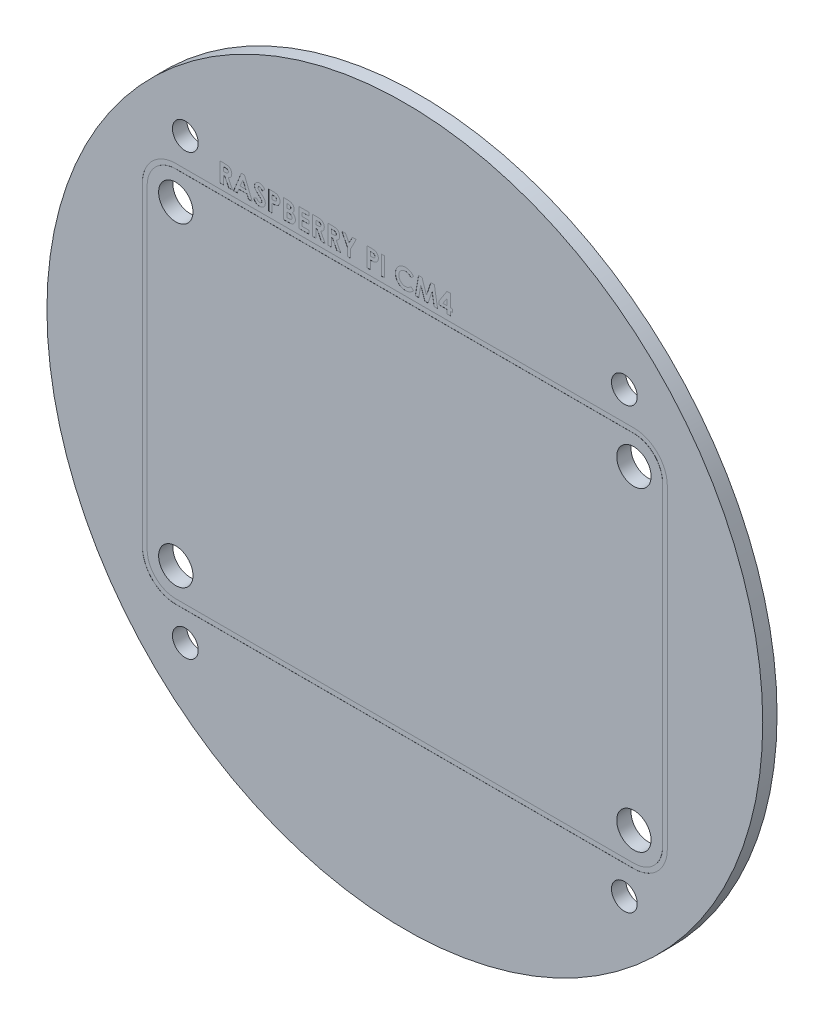
SolidWorks part; units mm, degrees
ref_plane "Plan de face" through (0, 0, 0) normal (0, 0, 1) x (1, 0, 0)
ref_plane "Plan de dessus" through (0, 0, 0) normal (0, 1, 0) x (1, 0, 0)
ref_plane "Plan de droite" through (0, 0, 0) normal (1, 0, 0) x (0, 0, -1)
sketch "Esquisse1" plane through (0, 0, 0) normal (0, 0, 1) x (1, 0, 0)
  line L1 (-23, -23) -> (23, -23) construction
  line L2 (-23, -23) -> (-23, 23) construction
  line L3 (-23, 23) -> (23, 23) construction
  line L4 (23, -23) -> (23, 23) construction
  line L5 (-23, -23) -> (23, 23) construction
  line L6 (-23, 23) -> (23, -23) construction
  line L7 (-24, -16.5) -> (24, -16.5) construction
  line L8 (-24, -16.5) -> (-24, 16.5) construction
  line L9 (-24, 16.5) -> (24, 16.5) construction
  line L10 (24, -16.5) -> (24, 16.5) construction
  line L11 (-24, -16.5) -> (24, 16.5) construction
  line L12 (-24, 16.5) -> (24, -16.5) construction
  circle A0 centre (0, 0) radius 37.5
  dimension "D3" = 75
  dimension "D1" = 48
  dimension "D2" = 46
  dimension "D4" = 33
extrude "Boss.-Extru.1" add sketch "Esquisse1" along normal blind 1.5
hole_wizard "Dégagement M2.51" positions "Esquisse2" profile "Esquisse3" hole size "M2.5" standard "ISO" end condition through all
sketch "Esquisse2" plane through (0, 0, 1.5) normal (0, 0, 1) x (1, 0, 0)
  point P0 (-23, 23)
  point P3 (23, 23)
  point P6 (23, -23)
  point P9 (-23, -23)
sketch "Esquisse3" plane through (-23, 23, 1.5) normal (1, 0, 0) x (0, -1, 0)
  line L0 (0, 0) -> (0, 1.5)
  line L1 (0, 1.5) -> (1.35, 1.5)
  line L2 (1.35, 1.5) -> (1.35, 0)
  line L5 (1.35, 0) -> (0, 0)
  line L11 (0, -6.35) -> (0, 107.95) construction
  dimension "Diamètre du perçage jusqu'au prochain" = 2.7
  dimension "Profondeur du perçage jusqu'au prochain" = 1.5
hole_wizard "Dégagement M31" positions "Esquisse4" profile "Esquisse5" hole size "M3" standard "ISO" end condition through all
sketch "Esquisse4" plane through (0, 0, 1.5) normal (0, 0, 1) x (1, 0, 0)
  point P0 (-24, 16.5)
  point P3 (24, 16.5)
  point P6 (24, -16.5)
  point P9 (-24, -16.5)
sketch "Esquisse5" plane through (-24, 16.5, 1.5) normal (1, 0, 0) x (0, -1, 0)
  line L0 (0, 0) -> (0, 1.5)
  line L1 (0, 1.5) -> (1.8, 1.5)
  line L2 (1.8, 1.5) -> (1.8, 0)
  line L5 (1.8, 0) -> (0, 0)
  line L11 (0, -6.35) -> (0, 107.95) construction
  dimension "Diamètre du perçage jusqu'au prochain" = 3.6
  dimension "Profondeur du perçage jusqu'au prochain" = 1.5
sketch "Esquisse6" plane through (0, 0, 1.5) normal (0, 0, 1) x (1, 0, 0)
  line L0 (-27.5, 16.5) -> (-27.5, -16.5)
  line L1 (-24, 19.5) -> (24, 19.5)
  line L2 (-27, 16.5) -> (-27, -16.5)
  line L3 (-24, -19.5) -> (24, -19.5)
  line L4 (27, 16.5) -> (27, -16.5)
  line L5 (-27, 19.5) -> (27, -19.5) construction
  line L6 (-27, -19.5) -> (27, 19.5) construction
  line L7 (-24, -20) -> (24, -20)
  line L8 (27.5, 16.5) -> (27.5, -16.5)
  line L9 (-24, 20) -> (24, 20)
  arc A0 (-27, -16.5) -> (-24, -19.5) centre (-24, -16.5) ccw
  arc A1 (24, -19.5) -> (27, -16.5) centre (24, -16.5) ccw
  arc A2 (24, 19.5) -> (27, 16.5) centre (24, 16.5) cw
  arc A3 (-24, 19.5) -> (-27, 16.5) centre (-24, 16.5) ccw
  circle A4 centre (-24, 16.5) radius 1.8 construction
  arc A5 (-27.5, -16.5) -> (-24, -20) centre (-24, -16.5) ccw
  arc A6 (24, -20) -> (27.5, -16.5) centre (24, -16.5) ccw
  arc A7 (24, 20) -> (27.5, 16.5) centre (24, 16.5) cw
  arc A8 (-24, 20) -> (-27.5, 16.5) centre (-24, 16.5) ccw
  point P0 (0, 0)
  point P6 (0, 0)
  point P19 (-24.1962, 16.3311)
  dimension "D1" = 3
  dimension "D2" = 0.5
extrude "Enlèv. mat.-Extru.1" cut sketch "Esquisse6" against normal blind 0.01
sketch "Esquisse7" plane through (0, 0, 1.5) normal (0, 0, 1) x (1, 0, 0)
  line L0 (-19.5963, 20.5548) -> (17.9051, 20.5548) construction
  text T0 "<b>RASPBERRY PI CM4</b>" font "Century Gothic" height 2
  point P2 (17.8709, 21.6196)
  point P3 (-20.3851, 20.9886)
  point P4 (5.3586, 20)
  point P5 (-19.5963, 20.5548)
  point P8 (18.4877, 20)
extrude "Enlèv. mat.-Extru.2" cut sketch "Esquisse7" against normal blind 0.01
